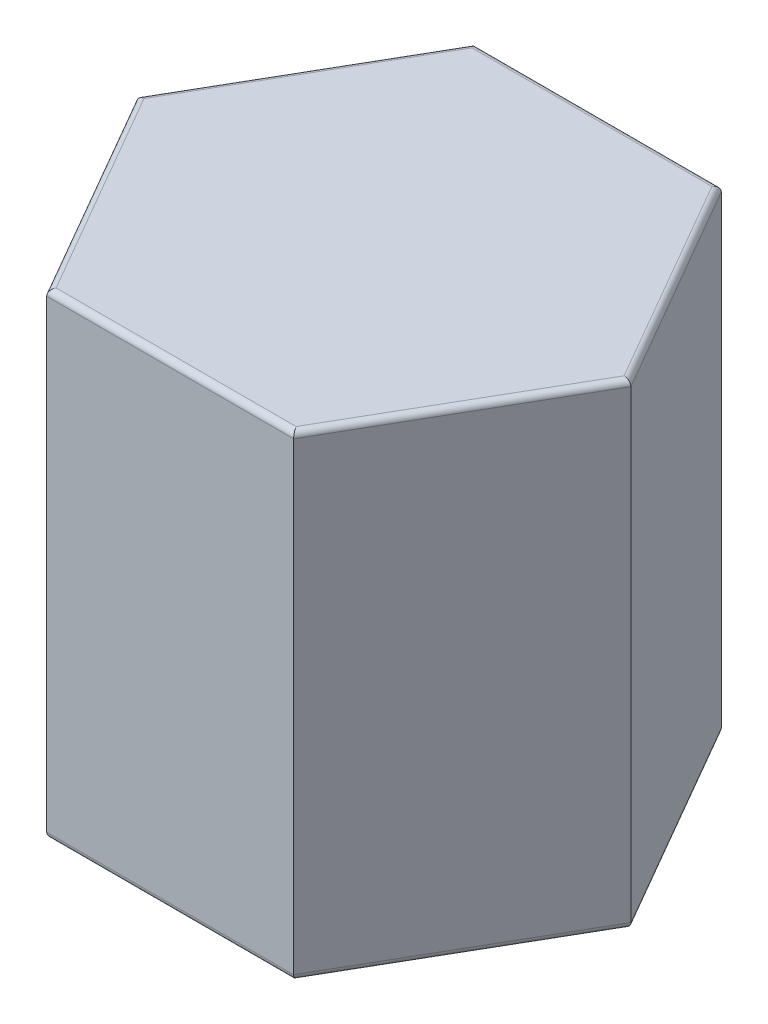
SolidWorks part; units mm, degrees
ref_plane "Front Plane" through (0, 0, 0) normal (0, 0, 1) x (1, 0, 0)
ref_plane "Top Plane" through (0, 0, 0) normal (0, 1, 0) x (1, 0, 0)
ref_plane "Right Plane" through (0, 0, 0) normal (1, 0, 0) x (0, 0, -1)
sketch "Sketch1" plane through (0, 0, 0) normal (0, 1, 0) x (1, 0, 0)
  line L1 (-10.375, 17.97) -> (-20.75, 0)
  line L2 (-20.75, 0) -> (-10.375, -17.97)
  line L3 (-10.375, -17.97) -> (10.375, -17.97)
  line L4 (10.375, -17.97) -> (20.75, 0)
  line L5 (20.75, 0) -> (10.375, 17.97)
  line L6 (10.375, 17.97) -> (-10.375, 17.97)
  circle A0 centre (0, 0) radius 17.97 construction
  dimension "D1" = 41.5
extrude "Boss-Extrude1" add sketch "Sketch1" along normal blind 40
fillet "Fillet1" radius 0.5 12 edges at (-15.5625, 0, -8.985) (-15.5625, 0, 8.985) (0, 0, 17.97) (15.5625, 0, 8.985) (15.5625, 0, -8.985) (0, 0, -17.97) (15.5625, 40, -8.985) (15.5625, 40, 8.985) (0, 40, 17.97) (-15.5625, 40, 8.985) (-15.5625, 40, -8.985) (0, 40, -17.97)
